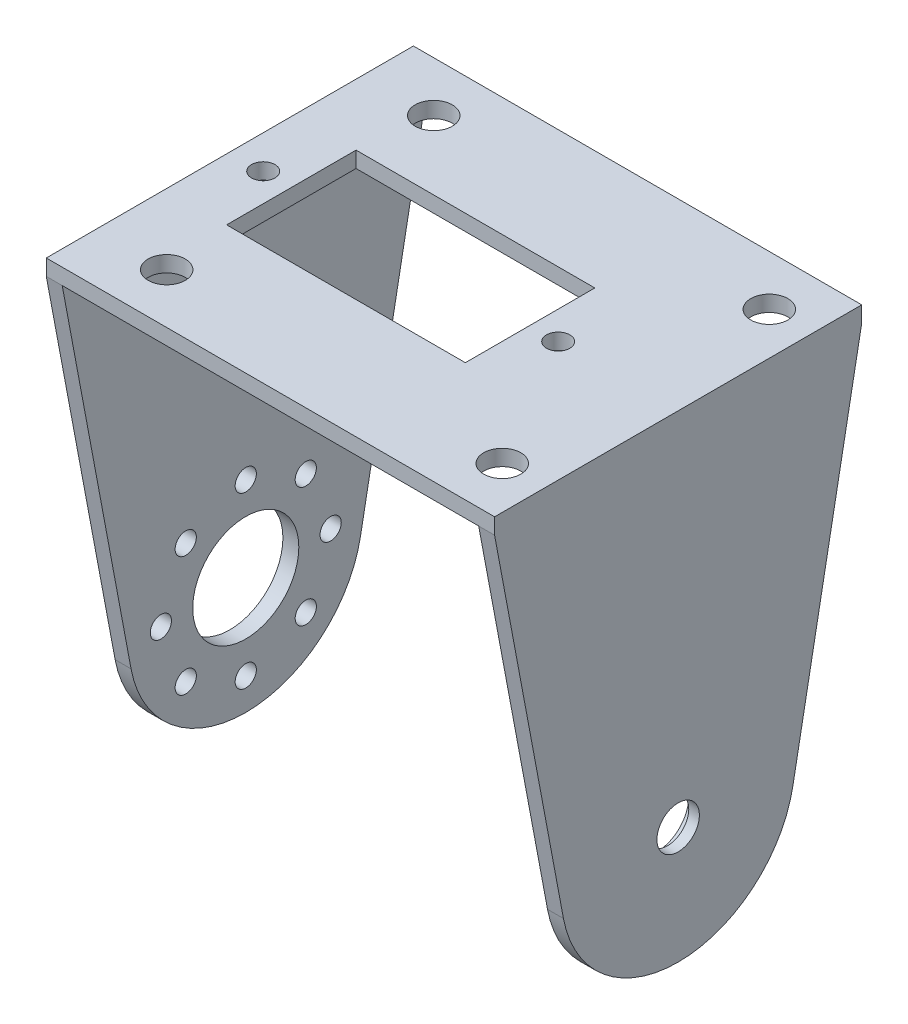
SolidWorks part; units mm, degrees
ref_plane "Front Plane" through (0, 0, 0) normal (0, 0, 1) x (1, 0, 0)
ref_plane "Top Plane" through (0, 0, 0) normal (0, 1, 0) x (1, 0, 0)
ref_plane "Right Plane" through (0, 0, 0) normal (1, 0, 0) x (0, 0, -1)
sketch "Sketch2" plane through (0, 0, 0) normal (1, 0, 0) x (0, 0, -1)
  line L0 (0, 0) -> (0, 32.5) construction
  line L1 (-17.3, 32.5) -> (17.3, 32.5)
  line L2 (-17.3, 32.5) -> (-10.8108, -2.0316)
  line L3 (17.3, 32.5) -> (10.8108, -2.0316)
  line L5 (-17.3, 32.5) -> (17.3, 32.5)
  line L6 (-17.3, 32.5) -> (-17.3, 34)
  line L7 (-17.3, 34) -> (17.3, 34)
  line L8 (17.3, 32.5) -> (17.3, 34)
  circle A0 centre (0, 0) radius 3
  circle A1 centre (0, 0) radius 4
  circle A2 centre (0, 0) radius 5
  circle A3 centre (0, 0) radius 11
  circle A4 centre (0, 0) radius 8 construction
  circle A5 centre (0, 8) radius 1
  circle A6 centre (5.6569, 5.6569) radius 1
  circle A7 centre (0, 0) radius 8 construction
  circle A8 centre (8, 0) radius 1
  circle A9 centre (0, 0) radius 8 construction
  circle A10 centre (5.6569, -5.6569) radius 1
  circle A11 centre (0, 0) radius 8 construction
  circle A12 centre (0, -8) radius 1
  circle A13 centre (0, 0) radius 8 construction
  circle A14 centre (-5.6569, -5.6569) radius 1
  circle A15 centre (0, 0) radius 8 construction
  circle A16 centre (-8, 0) radius 1
  circle A17 centre (0, 0) radius 8 construction
  circle A18 centre (-5.6569, 5.6569) radius 1
  circle A19 centre (0, 0) radius 8 construction
  point P11 (0, 32.5)
  point P40 (0, 0)
  dimension "D1" = 6
  dimension "D2" = 8
  dimension "D3" = 10
  dimension "D4" = 22
  dimension "D5" = 32.5
  dimension "D6" = 16
  dimension "D9" = 2
  dimension "D7" = 34.6
  dimension "D8" = 1.5
  dimension "D10" = 8
extrude "Boss-Extrude1" add sketch "Sketch2" along normal blind 1.5 contours A3 L3 L1 L2 | L1 L8 L7 L6 | A3 A18 A16 A14 A12 A10 A8 A6 A5 A2 region at (0, 33.25, 0) region at (0, 20.6944, 0) region at (0, 10.6428, 0.9913)
extrude "Boss-Extrude2" add sketch "Sketch2<3>" along normal blind 40.75 contours L1 L8 L7 L6 region at (0, 33.25, 0)
sketch "Sketch2<3>" plane through (0, 0, 0) normal (1, 0, 0) x (0, 0, -1) same geometry as "Sketch2"
extrude "Boss-Extrude3" add sketch "Sketch2<6>" along normal blind 1.5 from surface contours L1 L8 L7 L6 | A3 L3 L1 L2 | A3 A18 A16 A14 A12 A10 A8 A6 A5 A2 | A5 | A18 | A16 | A14 | A12 | A10 | A8 | A6 | A2 A1 | A1 A0 region at (0, 33.25, 0) region at (0, 20.6944, 0) region at (0, 10.6428, 0.9913) region at (0, 0, 3.8869) region at (0, 0, 4.8586) region at (0, 8, 0) region at (0, 5.6569, -5.6569) region at (0, 0, -8) region at (0, -5.6569, -5.6569) region at (0, -8, 0) region at (0, -5.6569, 5.6569) region at (0, 0, 8) region at (0, 5.6569, 5.6569) starting at face at (40.75, 33.25, 0)
sketch "Sketch2<6>" plane through (0, 0, 0) normal (1, 0, 0) x (0, 0, -1) same geometry as "Sketch2"
sketch "Sketch3" plane through (0, 34, 0) normal (0, 1, 0) x (1, 0, 0)
  line L0 (21.125, 17.3) -> (21.125, -17.3) construction
  line L1 (42.25, 17.3) -> (0, 17.3) construction
  line L2 (42.25, -17.3) -> (0, -17.3) construction
  line L3 (0, -17.3) -> (0, 17.3) construction
  line L8 (5.795, -6.1) -> (28.295, -6.1)
  line L9 (5.795, -6.1) -> (5.795, 6.1)
  line L10 (5.795, 6.1) -> (28.295, 6.1)
  line L11 (28.295, -6.1) -> (28.295, 6.1)
  line L12 (5.795, -6.1) -> (28.295, 6.1) construction
  line L13 (5.795, 6.1) -> (28.295, -6.1) construction
  line L14 (6.63, 12.5838) -> (38.2575, 12.5838) construction
  line L15 (6.63, 12.5838) -> (6.63, -12.5838) construction
  line L16 (6.63, -12.5838) -> (38.2575, -12.5838) construction
  line L17 (38.2575, 12.5838) -> (38.2575, -12.5838) construction
  line L18 (6.63, 0) -> (38.2575, 0) construction
  circle A2 centre (30.945, 0) radius 1.1
  circle A3 centre (3.145, 0) radius 1.1
  circle A4 centre (6.63, 12.5838) radius 1.75
  circle A5 centre (38.2575, 12.5838) radius 1.75
  circle A6 centre (38.2575, -12.5838) radius 1.75
  circle A7 centre (6.63, -12.5838) radius 1.75
  point P6 (21.125, 0)
  point P7 (17.045, 0)
  dimension "D3" = 12.2
  dimension "D4" = 2.2
  dimension "D6" = 2.65
  dimension "D11" = 3.5
  dimension "D1" = 4.08
  dimension "D2" = 22.5
  dimension "D5" = 2.65
  dimension "D7" = 31.6275
  dimension "D8" = 25.1676
  dimension "D10" = 6.63
extrude "Cut-Extrude1" cut sketch "Sketch3" against normal through all
extrude "Boss-Extrude4" add sketch "Sketch2<7>" against normal blind 0.5 from surface contours A1 A0 region at (0, 0, 3.8869) starting at face at (40.75, 0, -3)
sketch "Sketch2<7>" plane through (0, 0, 0) normal (1, 0, 0) x (0, 0, -1) same geometry as "Sketch2"
sketch "Sketch4" plane through (42.25, 0, 0) normal (1, 0, 0) x (0, 0, -1)
  circle A0 centre (0, 0) radius 3
  circle A1 centre (0, 0) radius 2
  circle A2 centre (0, 0) radius 3 construction
  dimension "D1" = 4
extrude "Boss-Extrude5" add sketch "Sketch4" against normal blind 1
